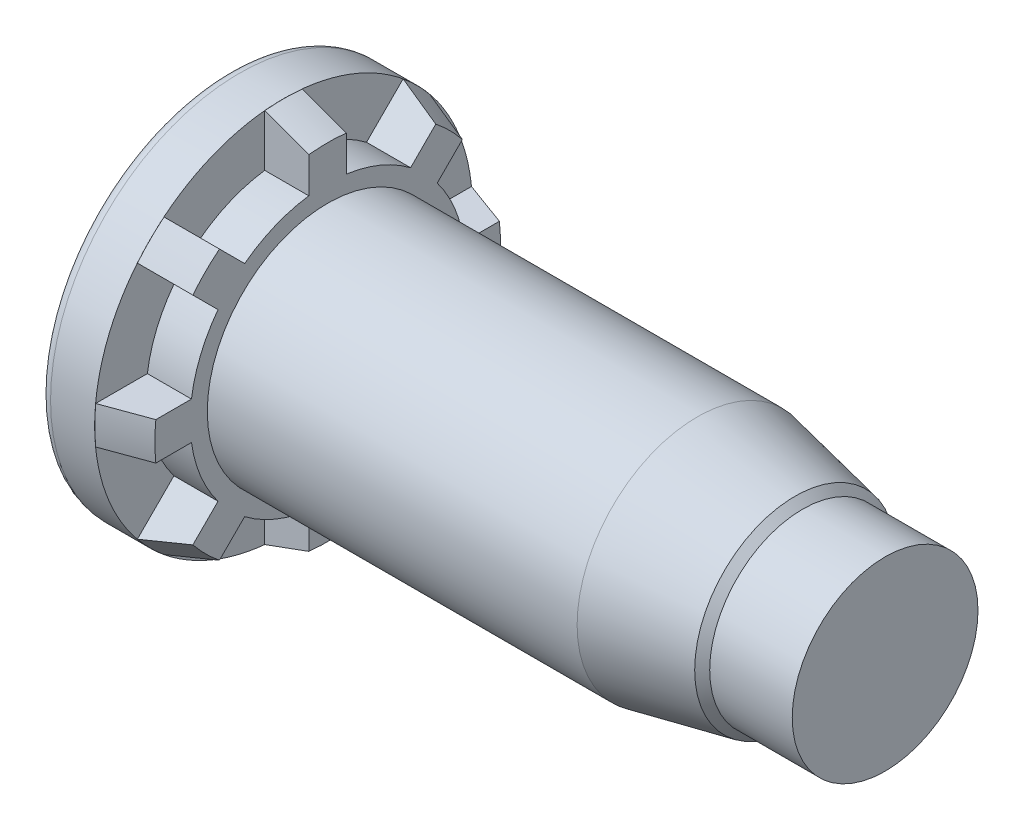
SolidWorks part; units mm, degrees
revolve "BaseBody" add sketch "BodySke" angle 360 about L6 other way angle 7.5
sketch "BodySke" plane through (0, 0, 0) normal (0, 0, 1) x (1, 0, 0)
  line L0 (-2.29, 7.392) -> (-2.29, 0)
  line L1 (1.832, 7.1816) -> (1.832, 5)
  line L2 (0.0025, 7.8475) -> (1.832, 7.1816)
  line L3 (1.832, 5) -> (17.2, 5)
  line L4 (17.2, 5) -> (21.258, 4.172)
  line L5 (25, 0) -> (-2.29, 0)
  line L6 (0, 0) -> (50.554, 0) construction
  line L7 (21.57, 3.86) -> (25, 3.86)
  line L8 (21.57, 3.86) -> (21.258, 4.172)
  line L9 (-1.832, 7.85) -> (0, 7.85)
  line L10 (0.0025, 7.8475) -> (0, 7.8475)
  line L11 (1.5, 19.05) -> (1.5, -3.175) construction
  line L12 (0, 7.8475) -> (0, 7.85)
  line L13 (25, 3.86) -> (25, 0)
  arc A0 (-2.29, 7.392) -> (-1.832, 7.85) centre (-1.832, 7.392) cw
  dimension "Fillet_rad" = 0.458
  dimension "T_dim" = 2.29
  dimension "H_dia" = 15.7
  dimension "D2" = 0.0025
  dimension "D3" = 0.0025
  dimension "Advance" = 1.5
  dimension "D1" = 20
  dimension "Length" = 25
  dimension "D4" = 45
  dimension "Diameter" = 10
  dimension "Minor_dia" = 8.344
cosmetic thread "ThreadCosmetic" [suppressed] parameters "Thread_length"=17.158, "Thread_minor"=8.344
ref_plane "Plane1" through (0, 0, 0) normal (0, 0, 1) x (1, 0, 0)
ref_plane "Plane2" through (0, 0, 0) normal (0, 1, 0) x (1, 0, 0)
ref_plane "Plane3" through (0, 0, 0) normal (1, 0, 0) x (0, 0, -1)
sketch "ThdSchSke" plane through (0, 0, 0) normal (0, 0, 1) x (1, 0, 0)
  line L0 (4.1, -4.172) -> (3.5202, -5)
  line L1 (4.1, -4.172) -> (4.6798, -5)
  line L2 (4.6798, -5) -> (4.6798, -6.25)
  line L3 (-3.175, 0) -> (5.1513, 0) construction
  line L4 (0, -7.85) -> (0, 7.85) construction
  line L5 (4.6798, -6.25) -> (3.5202, -6.25)
  line L6 (3.5202, -6.25) -> (3.5202, -5)
  line L7 (22.1518, 6.5809) -> (22.1518, 1.1961) construction
  dimension "Diameter" = 10
  dimension "Thread_minor" = 8.344
  dimension "Start" = 4.1
revolve "ThreadSchematic" [suppressed] cut sketch "ThdSchSke" angle 360 about L3
pattern_linear "ThdSchPat" [suppressed]
sketch "RibCutSke" plane through (1.832, 1.7944, -0.091) normal (1, 0, 0) x (0, 0, -1)
  line L0 (0.6912, 3.8643) -> (0.6912, 6.0165)
  line L1 (3.3573, 2.76) -> (4.8791, 4.2818)
  line L2 (0.6912, 3.144) -> (0.6912, 2.4006) construction
  line L3 (-0.091, -1.7944) -> (-0.091, 5.0239) construction
  line L4 (-0.091, -1.7944) -> (0.6912, 3.144) construction
  line L5 (-0.091, -1.7944) -> (2.848, 2.2507) construction
  line L6 (2.848, 2.2507) -> (2.3273, 1.73) construction
  arc A1 (3.3573, 2.76) -> (0.6912, 3.8643) centre (-0.091, -1.7944) ccw
  arc A2 (4.8791, 4.2818) -> (0.6912, 6.0165) centre (-0.091, -1.7944) ccw
  circle A3 centre (-0.091, -1.7944) radius 7.1816 construction
  circle A4 centre (-0.091, -1.7944) radius 5 construction
  dimension "Rib_root_half_angle" = 9
  dimension "Rib_root_gap_angle" = 27
  dimension "Angle" = 45
extrude "RibCut" cut sketch "RibCutSke" against normal blind 1.832
pattern_circular "RibCutsPat" count 8 every 45 about axis through (0, 0, 0) along (1, 0, 0) of "RibCut"
equation "' \"Length@BodySke\" = 25"
equation "' \"H_dia@BodySke\" = 15.7"
equation "' \"Start@ThdSchSke\" = 4.1"
equation "' \"T_dim@BodySke\" = 2.29"
equation "' \"Dog_dia@BodySke\" = 7.72"
equation "' \"Dog_len@BodySke\" = 3.43"
equation "' \"Thread_trans@BodySke\" = 4.37"
equation "' \"Diameter@BodySke\" = 10"
equation "' \"Minor_dia@BodySke\" =  8.344"
equation "' \"Minor_dia@BodySke\" = 8.344"
equation "' \"Advance@BodySke\" = 1.5"
equation "\"Fillet_rad@BodySke\" =  \"T_dim@BodySke\" * 0.2"
equation "\"Clinch_ht@BodySke\" = \"T_dim@BodySke\" * 0.8"
equation "\"Num_ribs@RibCutsPat\" = 8"
equation "\"Angle@RibCutSke\" =\"Angle@RibCutsPat\""
equation "\"Rib_root_half_angle@RibCutSke\" = \"Angle@RibCutSke\" / 5"
equation "\"Rib_root_gap_angle@RibCutSke\" = \"Angle@RibCutSke\" - (2 * \"Rib_root_half_angle@RibCutSke\" )"
equation "\"Rib_root_dia@RibCutSke\" = \"Diameter@BodySke\""
equation "\"Inner_dia@RibCutSke\" = \"Diameter@BodySke\" + ( \"H_dia@BodySke\" - \"Diameter@BodySke\" ) / 4"
equation "\"Outer_dia@RibCutSke\" = \"H_dia@BodySke\""
equation "\"Depth@RibCut\" = \"Clinch_ht@BodySke\""
equation "\"Thread_length@ThreadCosmetic\" = \"Length@BodySke\" - \"Start@ThdSchSke\"  - \"Dog_len@BodySke\"  - ( \"Minor_dia@BodySke\" - \"Dog_dia@BodySke\" ) / 2"
equation "\"Thread_minor@ThreadCosmetic\" = \"Minor_dia@BodySke\""
equation "\"Thread_minor@ThdSchSke\" = \"Minor_dia@BodySke\""
equation "\"Diameter@ThdSchSke\" = \"Diameter@BodySke\""
equation "\"Overcut@ThdSchSke\" = \"Diameter@BodySke\" * 1.25"
equation "\"Num_threads@ThdSchPat\" = int( \"Thread_length@ThreadCosmetic\" / \"Advance@BodySke\" + 0.999 )  + 1"
equation "\"Advance@ThdSchPat\" = \"Thread_length@ThreadCosmetic\" /  (\"Num_threads@ThdSchPat\" - 1) 'relax it"
equation "\"Num_threads@ThdSchPat\" = \"Num_threads@ThdSchPat\" - sgn( \"Num_threads@ThdSchPat\" - 1) '---chamfered tips only---"
